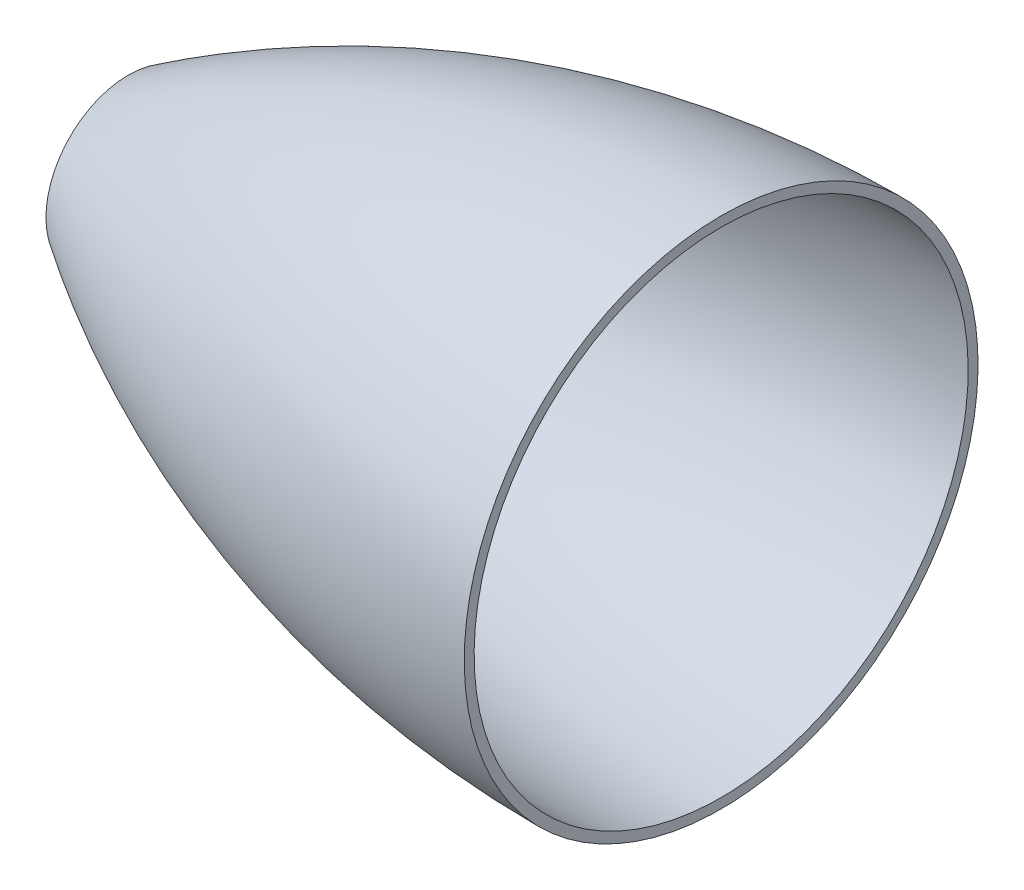
SolidWorks part; units mm, degrees
ref_plane "Front Plane" through (0, 0, 0) normal (0, 0, 1) x (1, 0, 0)
ref_plane "Top Plane" through (0, 0, 0) normal (0, 1, 0) x (1, 0, 0)
ref_plane "Right Plane" through (0, 0, 0) normal (1, 0, 0) x (0, 0, -1)
sketch "Sketch1" plane through (0, 0, 0) normal (0, 0, 1) x (1, 0, 0)
  line L0 (-860.683, 0) -> (-1040.683, 0) construction
  line L1 (-860.683, 78) -> (-860.683, -78) construction
  line L2 (-1040.683, 0) -> (-1040.683, 25)
  line L3 (189.317, 78) -> (-860.683, 78) construction
  line L4 (-1037.683, 0) -> (-1037.683, 23.36)
  line L5 (-860.683, 78) -> (-860.683, 75)
  line L6 (-1037.683, 0) -> (-1040.683, 0)
  arc A0 (-860.683, 78) -> (-1040.683, 25) centre (-860.683, -254.1604) ccw
  arc A1 (-860.683, 75) -> (-1037.683, 23.36) centre (-860.683, -254.1604) ccw
  dimension "D2" = 25
  dimension "D1" = 180
  dimension "D3" = 3
revolve "Revolve1" add sketch "Sketch1" angle 360 about L0
